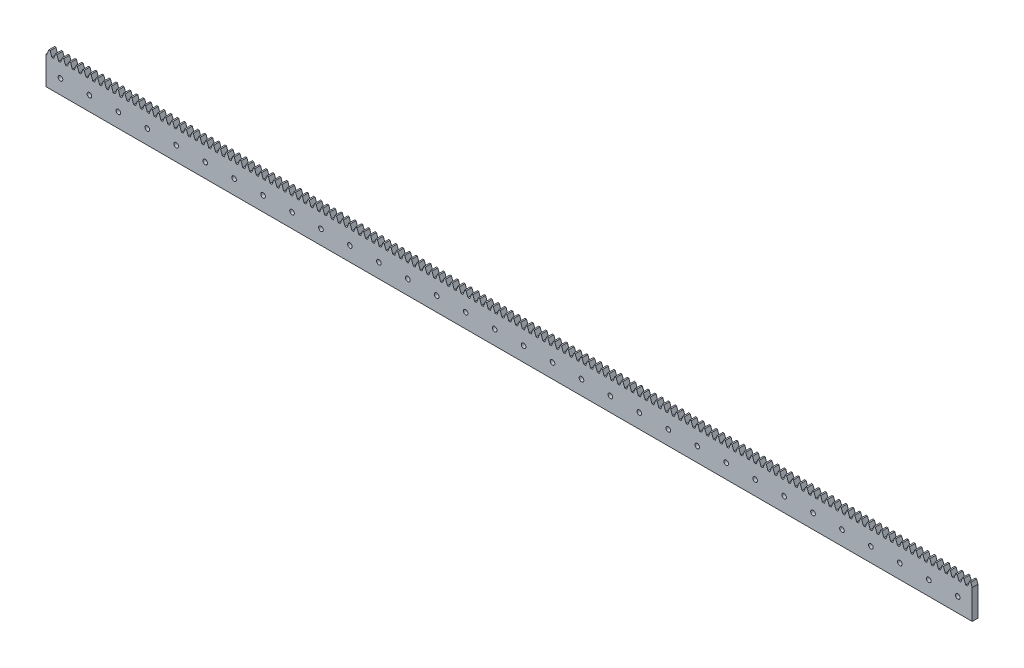
SolidWorks part; units mm, degrees
extrude "Blank" add sketch "BlankSke" against normal blind 4
sketch "BlankSke" plane through (0, 0, 0) normal (0, 0, 1) x (1, 0, 0)
  line L1 (0, 0) -> (640, 0)
  line L2 (0, 0) -> (0, 23)
  line L3 (0, 23) -> (640, 23)
  line L4 (640, 0) -> (640, 23)
  dimension "Length" = 640
ref_plane "Plane1" through (0, 0, 0) normal (0, 0, 1) x (1, 0, 0)
ref_plane "Plane2" through (0, 0, 0) normal (0, 1, 0) x (1, 0, 0)
ref_plane "Plane3" through (0, 0, 0) normal (1, 0, 0) x (0, 0, -1)
other "Configuration Table"
sketch "HoldingSke" plane through (0, 0, 0) normal (0, 1, 0) x (1, 0, 0)
  line L0 (0, 0) -> (0.0928, 0.6602)
  line L1 (-15, 0) -> (100, 0) construction
  line L2 (0, 0) -> (-2.1039, 2.3779)
  line L3 (0, 0) -> (-11.863, 4.5341)
  line L4 (0, 0) -> (-6.316, 5.8897)
  line L5 (0, 0) -> (-23.7986, -8.8762)
  line L6 (0, 0) -> (-10.5278, -7.1032)
  line L9 (-71.009, 38.7566) -> (530.3943, 257.6495)
  line L10 (-76.2, 3.8779) -> (-54.7, 3.8779)
  line L11 (0, 0) -> (-4, 0)
  line L12 (-76.2, 101.6) -> (-76.147, 101.6)
  line L13 (24.9733, 27.94) -> (52.9518, 28.4284)
  line L14 (24.9733, 27.94) -> (24.9743, 27.94)
  line L15 (24.9733, 27.94) -> (100.4006, 29.5858)
  circle A0 centre (0, 0) radius 19.05
  circle A1 centre (0, 0) radius 10.75
  circle A2 centre (0, 0) radius 12.7
  dimension "Num_teeth" = 137
  dimension "Width" = 4
  dimension "Length" = 640
  dimension "Pitch_height" = 21.5
sketch "TooCutSkeIll" plane through (0, 0, 0) normal (0, 0, 1) x (1, 0, 0)
  line L0 (-1.8687, 22.9605) -> (-0.7447, 19.8724)
  line L1 (-0.3914, 19.625) -> (0.3914, 19.625)
  line L2 (0.7447, 19.8724) -> (1.8687, 22.9605)
  line L3 (640, 23) -> (0, 23) construction
  line L4 (0, 0) -> (0, 64.897) construction
  line L5 (-13.208, 21.5) -> (12.954, 21.5) construction
  line L6 (0, 0) -> (640, 0) construction
  line L7 (1.3371, 21.5) -> (1.3371, 48.7463) construction
  line L8 (-1.3371, 21.5) -> (-1.3371, 48.7463) construction
  line L9 (1.9251, 23) -> (1.9251, 23.0254)
  line L10 (-1.9251, 23) -> (-1.9251, 23.0254)
  line L11 (-1.9251, 23.0254) -> (1.9251, 23.0254)
  arc A0 (0.3914, 19.625) -> (0.7447, 19.8724) centre (0.3914, 20.001) ccw
  arc A1 (-0.7447, 19.8724) -> (-0.3914, 19.625) centre (-0.3914, 20.001) ccw
  arc A2 (1.9251, 23) -> (1.8687, 22.9605) centre (1.9251, 22.94) ccw
  arc A3 (-1.8687, 22.9605) -> (-1.9251, 23) centre (-1.9251, 22.94) ccw
  dimension "Addendum_plus" = 1.5254
  dimension "Pitch_height" = 21.5
  dimension "Pressure_angle" = 20
  dimension "Gap_width" = 2.6742
  dimension "Dedendum" = 1.875
extrude "ToothCutIll" [suppressed] cut sketch "TooCutSkeIll" against normal through all
sketch "TooCutSkeSim" plane through (0, 0, 0) normal (0, 0, 1) x (1, 0, 0)
  line L0 (0.6547, 19.625) -> (-0.6547, 19.625)
  line L1 (1.8923, 23.0254) -> (0.6547, 19.625)
  line L2 (0, 17.4625) -> (0, 53.467) construction
  line L3 (1.8923, 23.0254) -> (-1.8923, 23.0254)
  line L6 (-1.8923, 23.0254) -> (-0.6547, 19.625)
  line L9 (-1.3371, 21.5) -> (1.3371, 21.5) construction
  line L10 (0, 0) -> (640, 0) construction
  line L11 (1.3371, 21.5) -> (1.3371, 53.467) construction
  line L12 (-1.3371, 21.5) -> (-1.3371, 53.467) construction
  dimension "Addendum_plus" = 1.5254
  dimension "Pitch_height" = 21.5
  dimension "Pressure_angle" = 20
  dimension "Gap_width" = 2.6742
  dimension "Dedendum" = 1.875
extrude "ToothCutSim" cut sketch "TooCutSkeSim" against normal through all
pattern_linear "TeethCuts" count 137 spacing 4.7124 along (1, 0, 0) of "ToothCutIll", "ToothCutSim"
sketch "草图1" plane through (0, 0, 0) normal (0, 0, 1) x (1, 0, 0)
  line L0 (0, 10) -> (640, 10) construction
  line L5 (0, 0) -> (640, 0) construction
  line L8 (0, 19.625) -> (0, 0) construction
  line L9 (640, 0) -> (640, 20.2576) construction
  line L10 (0, 19.625) -> (0, 0) construction
  circle A0 centre (10, 10) radius 1.6
  circle A1 centre (30, 10) radius 1.6
  circle A2 centre (50, 10) radius 1.6
  circle A3 centre (70, 10) radius 1.6
  circle A4 centre (90, 10) radius 1.6
  circle A5 centre (110, 10) radius 1.6
  circle A6 centre (130, 10) radius 1.6
  circle A7 centre (150, 10) radius 1.6
  circle A8 centre (170, 10) radius 1.6
  circle A9 centre (190, 10) radius 1.6
  circle A10 centre (210, 10) radius 1.6
  circle A11 centre (230, 10) radius 1.6
  circle A12 centre (250, 10) radius 1.6
  circle A13 centre (270, 10) radius 1.6
  circle A14 centre (290, 10) radius 1.6
  circle A15 centre (310, 10) radius 1.6
  circle A16 centre (330, 10) radius 1.6
  circle A17 centre (350, 10) radius 1.6
  circle A18 centre (370, 10) radius 1.6
  circle A19 centre (390, 10) radius 1.6
  circle A20 centre (410, 10) radius 1.6
  circle A21 centre (430, 10) radius 1.6
  circle A22 centre (450, 10) radius 1.6
  circle A23 centre (470, 10) radius 1.6
  circle A24 centre (490, 10) radius 1.6
  circle A25 centre (510, 10) radius 1.6
  circle A26 centre (530, 10) radius 1.6
  circle A27 centre (550, 10) radius 1.6
  circle A28 centre (570, 10) radius 1.6
  circle A29 centre (590, 10) radius 1.6
  circle A30 centre (610, 10) radius 1.6
  circle A31 centre (630, 10) radius 1.6
  dimension "D2" = 3.2
  dimension "D1" = 10
  dimension "D3" = 10
  dimension "D5" = 20
  dimension "D4" = 32
extrude "切除-拉伸1" cut sketch "草图1" against normal through all
equation "' \"Module@HoldingSke\" = 6.35"
equation "' \"Num_teeth@HoldingSke\" = 12"
equation "' \"Ap@HoldingSke\" =  20"
equation "' \"Ap@HoldingSke\" = 20"
equation "' \"Width@HoldingSke\" = 0.25 * 25.4"
equation "' \"Show_teeth@HoldingSke\" = 500"
equation "' \"Backlash@HoldingSke\" = 0.009 * 25.4"
equation "' \"Addendum_fac@HoldingSke\" = 1.0"
equation "' \"Dedendum_fac@HoldingSke\" = 1.25"
equation "' \"Dedendum_add@HoldingSke\" = 0.00005 * 25.4"
equation "' \"Clearance_fac@HoldingSke\" = 0.25"
equation "' \"Pitch_height@HoldingSke\" = 1 * 25.4"
equation "' \"Length@HoldingSke\" = 4.71 * 25.4"
equation "\"Pitch@HoldingSke\" = 1 / \"Module@HoldingSke\""
equation "\"MPH@HoldingSke\" = \"Dedendum_fac@HoldingSke\" / \"Pitch@HoldingSke\" + 2 * \"Dedendum_add@HoldingSke\" + 0.002 * 25.4"
equation "\"MPH@HoldingSke\" = ((sgn( \"MPH@HoldingSke\" - \"Pitch_height@HoldingSke\")+1)*( \"MPH@HoldingSke\" - \"Pitch_height@HoldingSke\"))/2 + \"Pitch_height@HoldingSke\""
equation "\"Blank_height@BlankSke\" = \"Pitch_height@HoldingSke\" + \"Addendum_fac@HoldingSke\"  / \"Pitch@HoldingSke\" "
equation "\"Length@BlankSke\" =  \"Length@HoldingSke\""
equation "\"Face_width@Blank\" = \"Width@HoldingSke\""
equation "\"Pressure_angle@TooCutSkeIll\" = \"Ap@HoldingSke\""
equation "\"Addendum_plus@TooCutSkeIll\" =  \"Addendum_fac@HoldingSke\"  / \"Pitch@HoldingSke\" + 0.001 *25.4"
equation "\"Dedendum@TooCutSkeIll\" = \"Dedendum_fac@HoldingSke\"  / \"Pitch@HoldingSke\""
equation "\"Pitch_height@TooCutSkeIll\" =  \"MPH@HoldingSke\""
equation "\"Gap_width@TooCutSkeIll\" = 3.14159265 / 2 / \"Pitch@HoldingSke\" + 6 * \"Backlash@HoldingSke\""
equation "\"Pressure_angle@TooCutSkeSim\" = \"Ap@HoldingSke\""
equation "\"Addendum_plus@TooCutSkeSim\" =  \"Addendum_fac@HoldingSke\"  / \"Pitch@HoldingSke\" + 0.001 * 25.4"
equation "\"Dedendum@TooCutSkeSim\" = \"Dedendum_fac@HoldingSke\"  / \"Pitch@HoldingSke\""
equation "\"Pitch_height@TooCutSkeSim\" =  \"MPH@HoldingSke\""
equation "\"Gap_width@TooCutSkeSim\" = 3.14159265 / 2 / \"Pitch@HoldingSke\" + 6 * \"Backlash@HoldingSke\""
equation "\"Root_fillet@TooCutSkeIll\" = \"Clearance_fac@HoldingSke\" / \"Pitch@HoldingSke\" + \"Dedendum_add@HoldingSke\""
equation "\"Break_rad@TooCutSkeIll\" = 0.02 / \"Pitch@HoldingSke\" * 2"
equation "\"Linear_pitch@TeethCuts\" = 3.14159265 / \"Pitch@HoldingSke\""
equation "\"Num_teeth@HoldingSke\" = int( ( \"Length@HoldingSke\" + 0 ) / (3.14159265 / \"Pitch@HoldingSke\")) + 0.9999  + 1"
equation " \"Num_teeth@TeethCuts\" = int( \"Show_teeth@HoldingSke\" ) + 1"
equation " \"Num_teeth@TeethCuts\" = ((sgn( \"Num_teeth@TeethCuts\" - \"Num_teeth@HoldingSke\" )-1)*( \"Num_teeth@TeethCuts\" - \"Num_teeth@HoldingSke\" ))/-2+ \"Num_teeth@HoldingSke\""
equation " \"Num_teeth@TeethCuts\" = ((sgn( \"Num_teeth@TeethCuts\" - 2.0)+1)*( \"Num_teeth@TeethCuts\" - 2.0))/2 +2.0"
